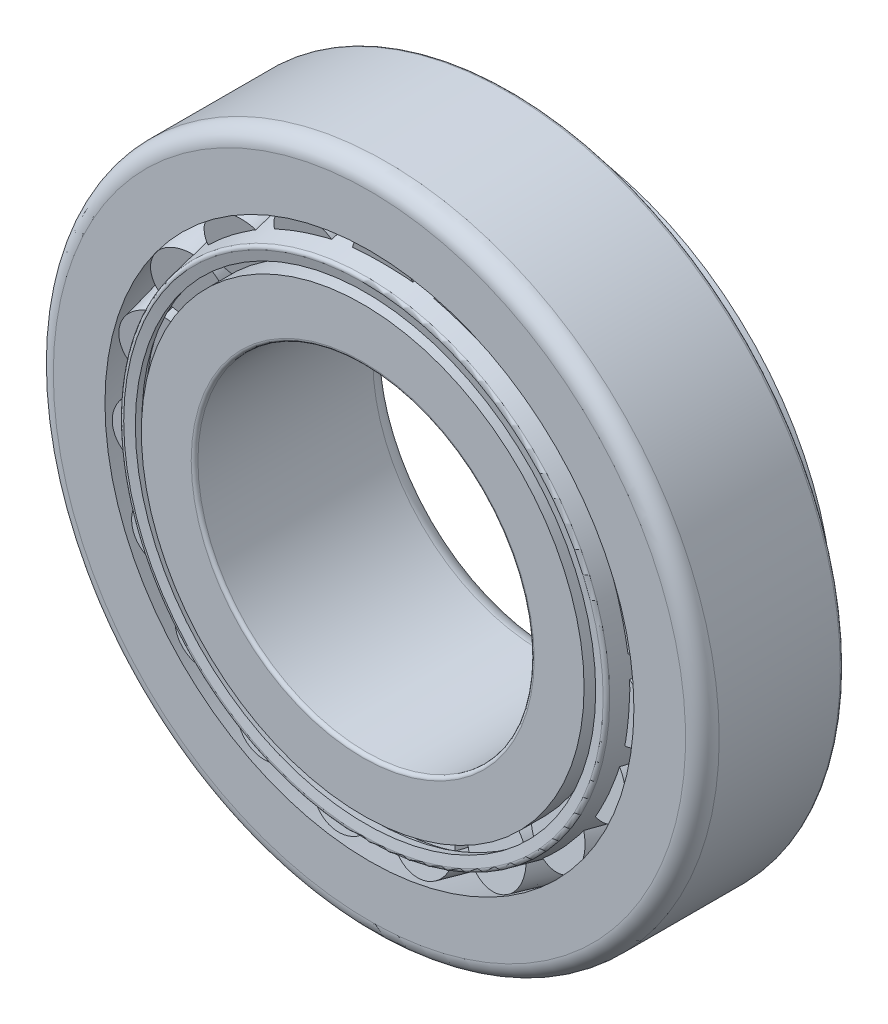
SolidWorks part; units mm, degrees
material "AISI 1020"
ref_plane "Front Plane" through (0, 0, 0) normal (0, 0, 1) x (1, 0, 0)
ref_plane "Top Plane" through (0, 0, 0) normal (0, 1, 0) x (1, 0, 0)
ref_plane "Right Plane" through (0, 0, 0) normal (1, 0, 0) x (0, 0, -1)
sketch "Sketch1" plane through (0, 0, 0) normal (1, 0, 0) x (0, 0, -1)
  line L0 (-5.334, 25.146) -> (-5.334, 19.975)
  line L1 (-5.334, 19.975) -> (5.334, 22.635)
  line L2 (5.334, 22.635) -> (5.334, 25.146)
  line L3 (5.334, 25.146) -> (-5.334, 25.146)
  line L4 (0, 0) -> (10110.1541, 0) construction
  line L5 (0.2596, 21.3697) -> (5.588, 0) construction
  line L6 (8.89, 18.63) -> (8.89, 12.7)
  line L7 (8.89, 12.7) -> (-5.842, 12.7)
  line L8 (-5.842, 12.7) -> (-5.842, 16.72)
  line L9 (-5.842, 16.72) -> (-3.9361, 16.72)
  line L10 (8.89, 18.63) -> (5.5242, 18.63)
  line L12 (8.89, 25.146) -> (-5.842, 25.146) construction
  line L14 (-5.842, 18.3534) -> (8.241, 21.434)
  line L15 (8.241, 21.434) -> (8.382, 20.7893)
  line L16 (8.382, 20.7893) -> (-5.0562, 17.8497)
  line L17 (-5.0562, 17.8497) -> (-4.9857, 17.5273)
  line L18 (-4.6836, 20.1372) -> (4.6836, 22.4728) construction
  line L19 (-5.842, 18.3534) -> (-5.6304, 17.3863)
  line L20 (-5.6304, 17.3863) -> (-4.9857, 17.5273)
  line L21 (4.6836, 22.4728) -> (5.8312, 17.2269)
  line L22 (5.8312, 17.2269) -> (-3.6558, 15.4383)
  line L23 (-3.6558, 15.4383) -> (-4.6836, 20.1372)
  line L25 (-4.1697, 17.7877) -> (5.2574, 19.8499) construction
  line L27 (0, 21.305) -> (0.5438, 18.8188) construction
  line L28 (0.5438, 18.8188) -> (1.0877, 16.3326) construction
  line L29 (-5.842, 25.146) -> (-5.842, 18.3534) construction
  point P7 (0, 25.146)
  point P44 (5.204, 20.0941)
  dimension "Width" = 10.668
  dimension "Inner Ring Width" = 14.732
  dimension "D17" = 0.33
  dimension "D2" = 0.25
  dimension "D3" = 14.732
  dimension "ID" = 25.4
  dimension "OD" = 50.292
  dimension "Cage Width" = 14.732
sketch "Sketch0" plane through (0, 0, 0) normal (0, 0, 1) x (1, 0, 0)
  circle A0 centre (0, 0) radius 12.7
  circle A1 centre (0, 0) radius 25.146
  dimension "D1" = 50.292
  dimension "D2" = 25.4
sketch "Sketch2" plane through (0, 0, 0) normal (1, 0, 0) x (0, 0, -1)
  line L0 (-5.334, 25.146) -> (-5.334, 19.975)
  line L1 (-5.334, 19.975) -> (5.334, 22.635)
  line L2 (5.334, 22.635) -> (5.334, 25.146)
  line L3 (5.334, 25.146) -> (-5.334, 25.146)
revolve "Revolve1" add sketch "Sketch2" angle 360 about L4
sketch "Sketch3" plane through (0, 0, 0) normal (1, 0, 0) x (0, 0, -1)
  line L0 (-5.842, 16.72) -> (-5.842, 12.7)
  line L1 (-5.842, 12.7) -> (8.89, 12.7)
  line L2 (8.89, 12.7) -> (8.89, 18.63)
  line L3 (8.89, 18.63) -> (5.5242, 18.63)
  line L4 (5.5242, 18.63) -> (5.8312, 17.2269)
  line L5 (5.8312, 17.2269) -> (-3.6558, 15.4383)
  line L6 (-3.6558, 15.4383) -> (-3.9361, 16.72)
  line L7 (-3.9361, 16.72) -> (-5.842, 16.72)
revolve "Revolve2" add sketch "Sketch3" angle 360 about L4
sketch "Sketch4" plane through (0, 0, 0) normal (1, 0, 0) x (0, 0, -1)
  line L0 (8.382, 20.7893) -> (8.241, 21.434)
  line L1 (8.241, 21.434) -> (-5.842, 18.3534)
  line L2 (-5.842, 18.3534) -> (-5.6304, 17.3863)
  line L3 (-5.6304, 17.3863) -> (-4.9857, 17.5273)
  line L4 (-4.9857, 17.5273) -> (-5.0562, 17.8497)
  line L5 (-5.0562, 17.8497) -> (8.382, 20.7893)
revolve "Revolve3" add sketch "Sketch4" angle 360 about L4
sketch "Sketch6" plane through (0, 0, 0) normal (1, 0, 0) x (0, 0, -1)
  line L0 (5.8312, 17.2269) -> (5.2574, 19.8499)
  line L1 (5.2574, 19.8499) -> (-4.1697, 17.7877)
  line L3 (-4.1697, 17.7877) -> (-3.6558, 15.4383)
  line L4 (-3.6558, 15.4383) -> (5.8312, 17.2269)
  line L5 (-4.1697, 17.7877) -> (5.2574, 19.8499) construction
  line L6 (-3.6558, 15.4383) -> (-4.6836, 20.1372) construction
revolve "Revolve4" add sketch "Sketch6" angle 360 about L25
pattern_circular "CirPattern1" count 19 over 360 about axis through (0, 0, 0) along (0, 0, -1) of "Revolve4"
fillet "Fillet1" radius 1.27 1 edges at (12.7, 0, -8.89)
fillet "Fillet2" radius 1.27 1 edges at (25.146, 0, 5.334)
fillet "Fillet3" radius 0.254 1 edges at (12.7, 0, 5.842)
fillet "Fillet4" radius 0.254 1 edges at (25.146, 0, -5.334)
fillet "Fillet5" radius 0.254 1 edges at (18.3534, 0, 5.842)
sketch "Sketch7" plane through (0, 0, 0) normal (1, 0, 0) x (0, 0, -1)
  line L0 (8.89, 18.63) -> (8.89, 12.7) construction
  line L1 (-5.842, 16.72) -> (-3.9361, 16.72) construction
  line L2 (-5.842, 12.7) -> (-5.842, 16.72) construction
  line L3 (8.89, 12.7) -> (-5.842, 12.7) construction
  line L4 (8.89, 18.63) -> (5.5242, 18.63) construction
  line L5 (5.8312, 17.2269) -> (-3.6558, 15.4383) construction
  line L6 (4.6836, 22.4728) -> (5.8312, 17.2269) construction
  line L7 (-5.334, 19.975) -> (5.334, 22.635) construction
  line L8 (-3.6558, 15.4383) -> (-4.6836, 20.1372) construction
  line L9 (8.89, 18.63) -> (8.89, 12.7)
  line L10 (-5.842, 16.72) -> (-3.9361, 16.72)
  line L11 (-5.842, 12.7) -> (-5.842, 16.72)
  line L12 (8.89, 12.7) -> (-5.842, 12.7)
  line L13 (8.89, 18.63) -> (5.5242, 18.63)
  line L14 (5.8312, 17.2269) -> (-3.6558, 15.4383)
  line L15 (4.6836, 22.4728) -> (5.8312, 17.2269)
  line L16 (-4.6836, 20.1372) -> (4.6836, 22.4728)
  line L17 (-3.6558, 15.4383) -> (-4.6836, 20.1372)
  line L18 (0, 0) -> (-5.5939, 0) construction
  line L19 (-200000, 0) -> (210110.1541, 0) construction
  line L20 (-5.5939, -18.4077) -> (-5.5939, 18.4077) construction
  line L21 (-3.6558, -15.4383) -> (-4.6836, -20.1372)
  line L22 (-4.6836, -20.1372) -> (4.6836, -22.4728)
  line L23 (4.6836, -22.4728) -> (5.8312, -17.2269)
  line L24 (5.8312, -17.2269) -> (-3.6558, -15.4383)
  line L25 (8.89, -18.63) -> (5.5242, -18.63)
  line L26 (8.89, -12.7) -> (-5.842, -12.7)
  line L27 (-5.842, -12.7) -> (-5.842, -16.72)
  line L28 (-5.842, -16.72) -> (-3.9361, -16.72)
  line L29 (8.89, -18.63) -> (8.89, -12.7)
move or copy body "Body-Move/Copy1" [suppressed] bodies to move or copy 104 copy no translate (0, 0, 33.3375)
ref_plane "Contact Plane 1" through (0, 0, 5.334) normal (0, 0, 1) x (1, 0, 0)
ref_plane "Contact Plane 2" through (0, 0, -5.334) normal (0, 0, -1) x (-1, 0, 0)
ref_axis "Center Axis 1" through (0, 0, -7.62) along (0, 0, 1)
equation "\"D17@Sketch1\" = \"Cone Thick@Sketch1\" / 2"
equation "\"D1@Fillet4\"=\"D1@Fillet3\""
equation "\"D1@Fillet5\"=\"D1@Fillet4\""
